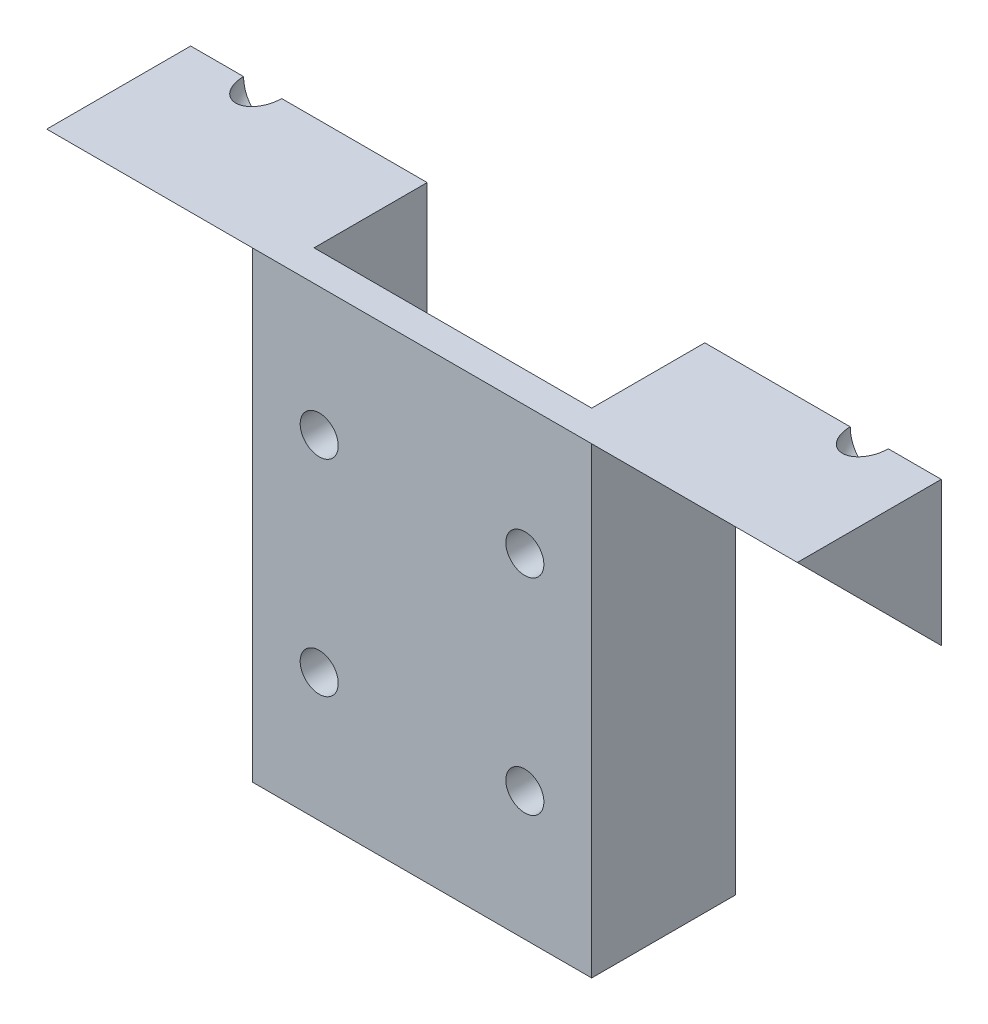
SolidWorks part; units mm, degrees
ref_plane "Front Plane" through (0, 0, 0) normal (0, 0, 1) x (1, 0, 0)
ref_plane "Top Plane" through (0, 0, 0) normal (0, 1, 0) x (1, 0, 0)
ref_plane "Right Plane" through (0, 0, 0) normal (1, 0, 0) x (0, 0, -1)
sketch "Sketch1" plane through (0, 0, 0) normal (0, 0, 1) x (1, 0, 0)
  line L1 (-16.5, -22.5) -> (16.5, -22.5)
  line L2 (-16.5, -22.5) -> (-16.5, 22.5)
  line L3 (-16.5, 22.5) -> (16.5, 22.5)
  line L4 (16.5, -22.5) -> (16.5, 22.5)
  line L5 (-16.5, -22.5) -> (16.5, 22.5) construction
  line L6 (-16.5, 22.5) -> (16.5, -22.5) construction
  point P0 (0, 0)
  dimension "D1" = 33
  dimension "D2" = 45
extrude "Boss-Extrude1" add sketch "Sketch1" along normal blind 14
sketch "Sketch2" plane through (0, 0, 0) normal (0, 0, 1) x (1, 0, 0)
  line L0 (16.5, 22.5) -> (-16.5, 22.5) construction
  line L1 (13.5, -22.5) -> (-13.5, -22.5)
  line L2 (13.5, -22.5) -> (13.5, 22.5)
  line L3 (13.5, 22.5) -> (-13.5, 22.5)
  line L4 (-13.5, -22.5) -> (-13.5, 22.5)
  line L5 (13.5, -22.5) -> (-13.5, 22.5) construction
  line L6 (13.5, 22.5) -> (-13.5, -22.5) construction
  line L7 (16.5, -22.5) -> (16.5, 22.5) construction
  point P0 (0, 0)
  dimension "D1" = 3
extrude "Cut-Extrude1" cut sketch "Sketch2" along normal offset from surface (11 mm away) 3 up to face at (0, 0, 14)
sketch "Sketch3" plane through (0, 0, 14) normal (0, 0, 1) x (1, 0, 0)
  line L1 (-10, -10) -> (10, -10) construction
  line L2 (-10, -10) -> (-10, 10) construction
  line L3 (-10, 10) -> (10, 10) construction
  line L4 (10, -10) -> (10, 10) construction
  line L5 (-10, -10) -> (10, 10) construction
  line L6 (-10, 10) -> (10, -10) construction
  circle A0 centre (-10, 10) radius 1.85
  circle A1 centre (10, 10) radius 1.85
  circle A2 centre (10, -10) radius 1.85
  circle A3 centre (-10, -10) radius 1.85
  point P0 (0, 0)
  dimension "D3" = 3.7
  dimension "D1" = 20
  dimension "D2" = 20
extrude "Cut-Extrude2" cut sketch "Sketch3" against normal blind 10
sketch "Sketch4" plane through (-16.5, 0, 0) normal (-1, 0, 0) x (0, 0, 1)
  line L5 (0, 22.5) -> (0, 8.5)
  line L6 (0, 22.5) -> (0, -22.5) construction
  line L7 (0, 8.5) -> (14, 22.5)
  line L8 (14, 22.5) -> (0, 22.5)
  dimension "D1" = 14
extrude "Boss-Extrude2" add sketch "Sketch4" along normal blind 20
mirror "Mirror1" about plane through (0, 0, 0) normal (1, 0, 0) of "Boss-Extrude2"
sketch "Sketch5" plane through (0, 4.25, -4.25) normal (0, -0.7071, 0.7071) x (1, 0, 0)
  line L0 (-36.5, 15.9099) -> (-16.5, 15.9099) construction
  line L1 (-36.5, 6.0104) -> (-36.5, 25.8094) construction
  line L2 (-16.5, 6.0104) -> (-16.5, 25.8094) construction
  line L3 (36.5, 15.9099) -> (16.5, 15.9099) construction
  line L4 (16.5, 6.0104) -> (16.5, 25.8094) construction
  circle A0 centre (-29.5, 15.9099) radius 1.85
  circle A1 centre (29.5, 15.9099) radius 1.85
  dimension "D1" = 3.7
  dimension "D2" = 7
  dimension "D3" = 7
extrude "Cut-Extrude3" cut sketch "Sketch5" against normal through all
